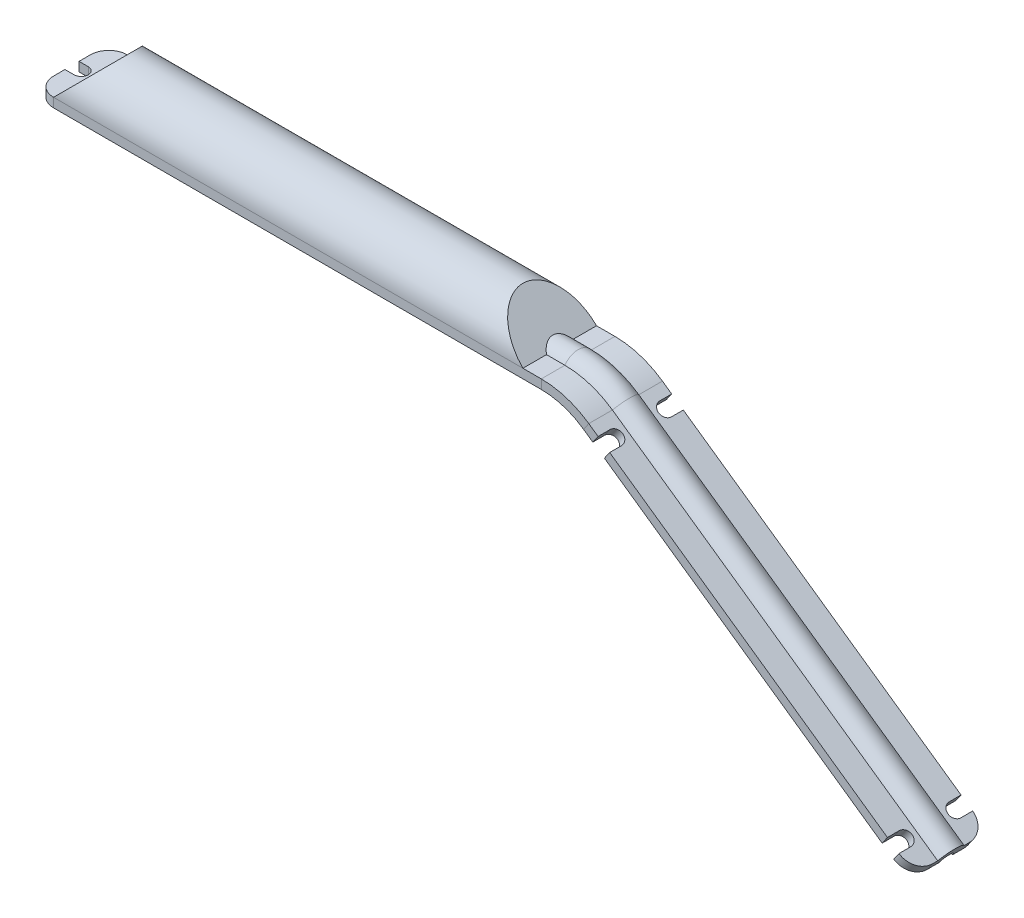
SolidWorks part; units mm, degrees
material "Polycarbonate"
ref_plane "Front Plane" through (0, 0, 0) normal (0, 0, 1) x (1, 0, 0)
ref_plane "Top Plane" through (0, 0, 0) normal (0, 1, 0) x (1, 0, 0)
ref_plane "Right Plane" through (0, 0, 0) normal (1, 0, 0) x (0, 0, -1)
sketch "Sketch1" plane through (0, -59.2688, 0) normal (-1, 0, 0) x (0, 0, -1)
  line L2 (-6.35, -59.2688) -> (-1.1906, -59.2688)
  line L5 (1.1906, -59.2688) -> (6.35, -59.2688)
  line L6 (6.35, -59.2688) -> (6.35, -60.8563)
  line L7 (6.35, -60.8563) -> (2.2799, -60.8563)
  line L8 (-6.35, -59.2688) -> (-6.35, -60.8563)
  line L9 (-6.35, -60.8563) -> (-2.2799, -60.8563)
  arc A2 (1.1906, -59.2688) -> (-1.1906, -59.2688) centre (0, -59.2688) cw
  arc A3 (2.2799, -60.8563) -> (-2.2799, -60.8563) centre (0, -59.2688) cw
  dimension "D2" = 1.1906
  dimension "D3" = 12.7
  dimension "D4" = 1.5875
  dimension "D1" = 1.5875
sketch "Sketch2" plane through (0, 0, 0) normal (0, 0, 1) x (1, 0, 0)
  line L8 (-3.175, 0) -> (6.35, 0)
  line L9 (13.6344, -2.2968) -> (69.7494, -41.5889)
  arc A6 (6.35, 0) -> (13.6344, -2.2968) centre (6.35, -12.7) cw
  dimension "D2" = 12.7
  dimension "D1" = 9.525
  dimension "D3" = 145
  dimension "D4" = 68.5038
  dimension "D5" = 6.35
sketch "Sketch15" plane through (0, 0, 0) normal (1, 0, 0) x (0, 0, -1)
  line L0 (6.35, 0) -> (-6.35, 0)
  line L1 (6.35, 0) -> (6.35, 1.5875)
  line L3 (-6.35, 0) -> (-6.35, 1.5875)
  arc A0 (6.35, 1.5875) -> (-6.35, 1.5875) centre (0, 1.5875) ccw
  point P5 (0, 0)
  dimension "D1" = 12.7
  dimension "D3" = 1.5875
extrude "Boss-Extrude1" add sketch "Sketch15" against normal blind 80.9625 and the other way blind 3.175
sketch "Sketch16" plane through (-25.1185, -23.5169, -8.3085) normal (0, 0, -1) x (1, 0, 0)
  line L0 (-55.844, -25.1044) -> (-52.669, -25.1044)
  line L2 (-55.844, -31.4544) -> (28.2935, -31.4544) construction
  line L3 (-55.844, -31.4544) -> (28.2935, -31.4544) construction
  line L9 (-46.319, -31.4544) -> (-55.844, -31.4544)
  line L10 (-55.844, -31.4544) -> (-55.844, -25.1044)
  line L11 (28.2935, -31.4544) -> (28.2935, -25.1044)
  line L12 (28.2935, -25.1044) -> (21.9435, -31.4544)
  line L13 (21.9435, -31.4544) -> (28.2935, -31.4544)
  line L14 (-52.669, -25.1044) -> (-46.319, -31.4544)
  line L15 (28.2935, -23.5169) -> (-55.844, -23.5169) construction
  dimension "D1" = 1.5875
  dimension "D2" = 45
  dimension "D3" = 1.5875
  dimension "D4" = 3.175
  dimension "D5" = 45
extrude "Cut-Extrude1" cut sketch "Sketch16" against normal through all
sweep "Sweep3" add profiles "Sketch1" path "Sketch2"
ref_plane "Plane2" through (-40.4812, 0, 0) normal (-1, 0, 0) x (0, 0, 1)
sketch "Sketch17" plane through (-40.4812, 0, 0) normal (-1, 0, 0) x (0, 0, 1)
  line L0 (-4.7625, 0) -> (4.7625, 0)
  line L1 (-4.7625, 0) -> (-4.7625, 1.5875)
  line L2 (4.7625, 0) -> (4.7625, 1.5875)
  line L3 (-6.35, 0) -> (-6.35, 1.5875) construction
  arc A0 (-4.7625, 1.5875) -> (4.7625, 1.5875) centre (0, 1.5875) cw
  arc A2 (6.35, 1.5875) -> (-6.35, 1.5875) centre (0, 1.5875) ccw construction
  arc A3 (6.35, 1.5875) -> (-6.35, 1.5875) centre (0, 1.5875) ccw construction
  point P4 (0, 0)
  dimension "D1" = 1.5875
extrude "Cut-Extrude2" cut sketch "Sketch17" against normal offset from surface 1.5875 and the other way offset from surface 1.5875 up to face at (1.2898, 3.4727, 0) other way up to face at (-74.6125, 4.7625, 0)
fillet "Fillet2" radius 3.175 2 edges at (-80.9625, 0.7938, 6.35) (-80.9625, 0.7938, -6.35)
sketch "Sketch20" plane through (0, 1.5875, 0) normal (0, 1, 0) x (1, 0, 0)
  line L0 (3.5433, -6.35) -> (3.5433, -4.3149) construction
  line L1 (3.175, -6.35) -> (6.35, -6.35) construction
  line L2 (5.9817, -6.35) -> (5.9817, -4.3149) construction
  line L3 (3.175, -2.2799) -> (6.35, -2.2799) construction
  line L4 (6.35, -6.35) -> (6.35, -2.2799) construction
  line L5 (3.5433, 6.35) -> (3.5433, 4.3149) construction
  line L6 (3.175, 6.35) -> (6.35, 6.35) construction
  line L7 (5.9817, 6.35) -> (5.9817, 4.3149) construction
  line L8 (-77.7875, -6.35) -> (-77.7875, 6.35) construction
  line L9 (-79.375, 1.2192) -> (-80.9625, 1.2192)
  line L10 (-80.9625, -3.175) -> (-80.9625, 3.175) construction
  line L11 (-79.375, -1.2192) -> (-80.9625, -1.2192)
  line L12 (-80.9625, 1.2192) -> (-80.9625, -1.2192)
  line L13 (-80.9625, 0) -> (-77.7875, 0) construction
  line L14 (3.5433, -6.35) -> (5.9817, -6.35) construction
  line L15 (3.5433, 6.35) -> (5.9817, 6.35) construction
  arc A0 (3.5433, -4.3149) -> (5.9817, -4.3149) centre (4.7625, -4.3149) cw construction
  arc A1 (3.5433, 4.3149) -> (5.9817, 4.3149) centre (4.7625, 4.3149) ccw construction
  circle A2 centre (-79.375, 0) radius 1.2192 construction
  arc A3 (-79.375, 1.2192) -> (-79.375, -1.2192) centre (-79.375, 0) cw
  point P9 (4.7625, -2.2799)
  point P12 (6.35, -4.3149)
  point P25 (-77.7875, 0)
  dimension "D1" = 1.2192
  dimension "D2" = 2.4384
extrude "Cut-Extrude3" cut sketch "Sketch20" against normal through all
fillet "Fillet6" radius 3.175 2 edges at (70.2047, -40.9387, 6.35) (70.2047, -40.9387, -6.35)
sketch "Sketch22" plane through (4.317, 6.1653, 0) normal (0.5736, 0.8192, 0) x (0.8192, -0.5736, 0)
  line L0 (12.486, 2.2799) -> (12.486, 6.35) construction
  line L1 (12.486, -6.35) -> (12.486, -2.2799) construction
  line L3 (77.8148, 4.3149) -> (77.8148, 6.35)
  line L4 (12.486, 6.35) -> (77.8148, 6.35) construction
  line L5 (75.3764, 4.3149) -> (75.3764, 6.35)
  line L6 (75.3764, 6.35) -> (77.8148, 6.35)
  line L7 (75.3764, -4.3149) -> (75.3764, -6.35)
  line L8 (12.486, -6.35) -> (77.8148, -6.35) construction
  line L9 (77.8148, -4.3149) -> (77.8148, -6.35)
  line L10 (75.3764, -6.35) -> (77.8148, -6.35)
  line L11 (14.4418, 4.3149) -> (14.4418, 6.35)
  line L12 (14.4418, 6.35) -> (16.8802, 6.35)
  line L13 (16.8802, 6.35) -> (16.8802, 4.3149)
  line L14 (14.4418, -4.3149) -> (14.4418, -6.35)
  line L15 (14.4418, -6.35) -> (16.8802, -6.35)
  line L16 (16.8802, -6.35) -> (16.8802, -4.3149)
  arc A0 (75.3764, 4.3149) -> (77.8148, 4.3149) centre (76.5956, 4.3149) ccw
  arc A1 (77.8148, -4.3149) -> (75.3764, -4.3149) centre (76.5956, -4.3149) ccw
  arc A2 (14.4418, 4.3149) -> (16.8802, 4.3149) centre (15.661, 4.3149) ccw
  arc A3 (16.8802, -4.3149) -> (14.4418, -4.3149) centre (15.661, -4.3149) ccw
  point P10 (12.486, 4.3149)
  point P13 (12.486, -4.3149)
  dimension "D1" = 2.4384
  dimension "D2" = 3.175
extrude "Cut-Extrude6" cut sketch "Sketch22" against normal through all
